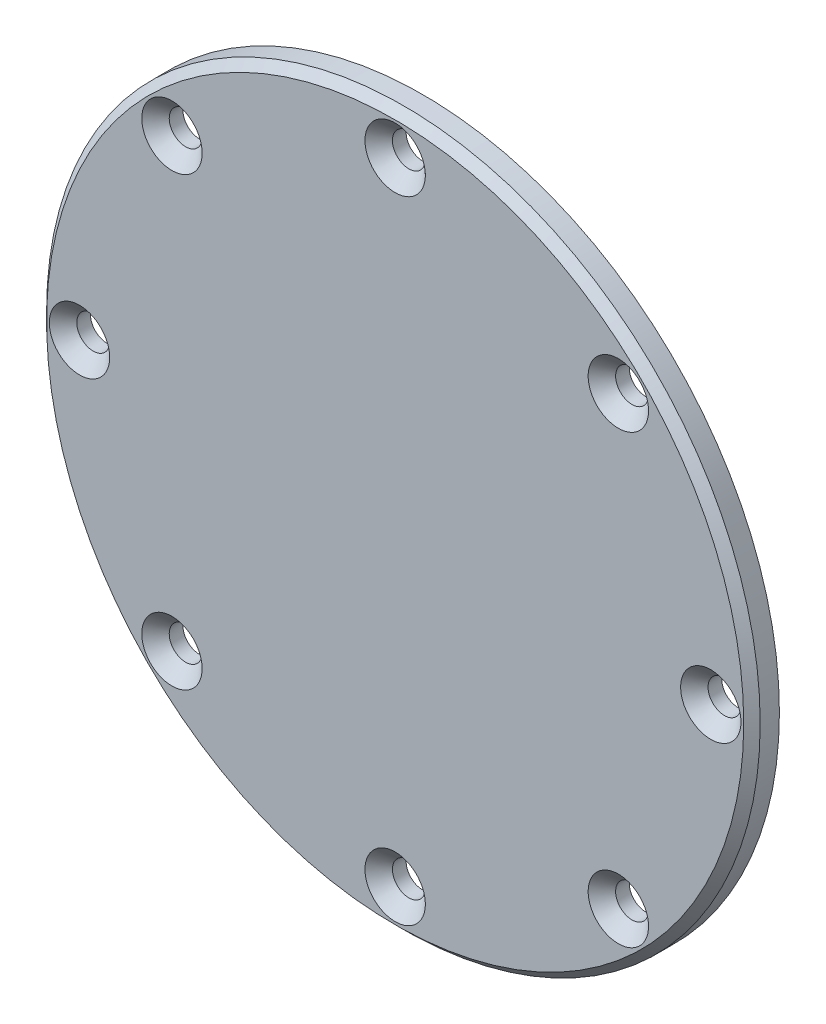
SolidWorks part; units mm, degrees
material "ABS"
ref_plane "Спереди" through (0, 0, 0) normal (0, 0, 1) x (1, 0, 0)
ref_plane "Сверху" through (0, 0, 0) normal (0, 1, 0) x (1, 0, 0)
ref_plane "Справа" through (0, 0, 0) normal (1, 0, 0) x (0, 0, -1)
sketch "Эскиз1" plane through (0, 0, 0) normal (0, 0, 1) x (1, 0, 0)
  circle A0 centre (0, 0) radius 26
  dimension "D1" = 52
extrude "Бобышка-Вытянуть1" add sketch "Эскиз1" along normal blind 2
chamfer "Фаска2" distance 0.6 angle 45 1 edges at (26, 0, 2)
hole_wizard "Зенковка для винта с полупотайной головкой M21" positions "Эскиз2" profile "Эскиз3" countersink size "M2" standard "DIN"
sketch "Эскиз2" plane through (0, 0, 2) normal (0, 0, 1) x (1, 0, 0)
  line L0 (-23, 0) -> (23, 0) construction
  circle A0 centre (0, 0) radius 23 construction
  point P0 (-23, 0)
  point P11 (0, 0)
  point P12 (-23, 0)
  dimension "D1" = 46
sketch "Эскиз3" plane through (-23, 0, 2) normal (1, 0, 0) x (0, -1, 0)
  line L0 (0, 0) -> (0, 6.721)
  line L1 (0, 6.721) -> (1.2, 6)
  line L2 (1.2, 6) -> (1.2, 1)
  line L3 (1.2, 1) -> (2.2, 0)
  line L5 (2.2, 0) -> (0, 0)
  line L6 (-1.2, 1) -> (-2.2, 0) construction
  line L10 (0, 6.721) -> (-1.2, 6) construction
  line L11 (0, -6.35) -> (0, 107.95) construction
  dimension "Диаметр отверстия" = 2.4
  dimension "Глубина отверстия" = 6
  dimension "Диаметр передней зенковки" = 4.4
  dimension "Угол передней зенковки" = 90
  dimension "Угол заточки сверла" = 118
pattern_circular "Круговой массив1" count 8 over 360 about axis through (0, 0, 2) along (0, 0, 1) of "Зенковка для винта с полупотайной головкой M21"
